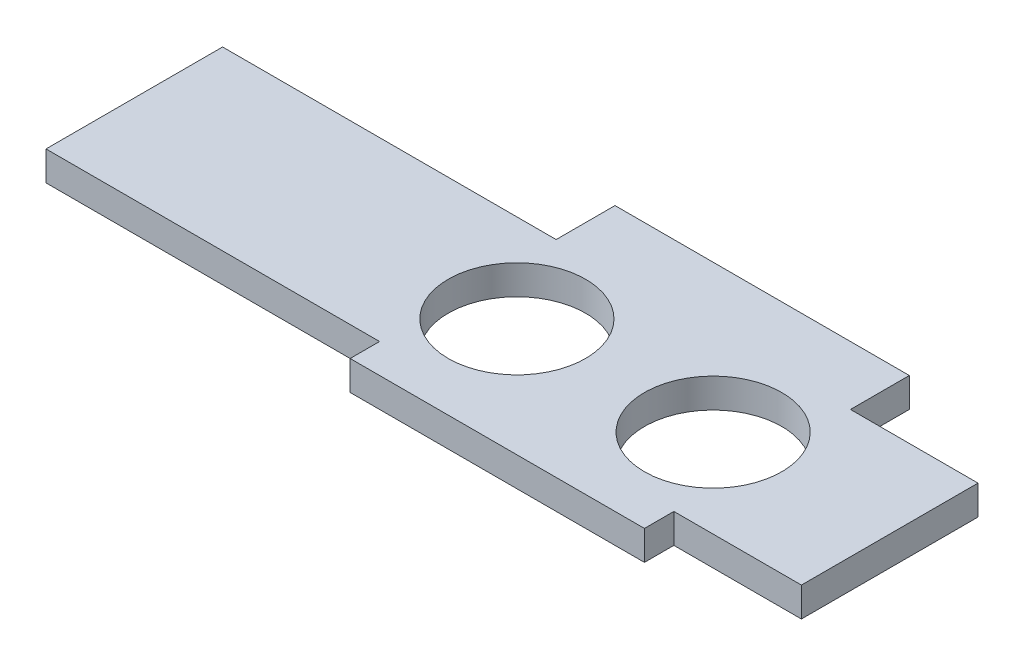
SolidWorks part; units mm, degrees
ref_plane "Front Plane" through (0, 0, 0) normal (0, 0, 1) x (1, 0, 0)
ref_plane "Top Plane" through (0, 0, 0) normal (0, 1, 0) x (1, 0, 0)
ref_plane "Right Plane" through (0, 0, 0) normal (1, 0, 0) x (0, 0, -1)
sketch "Sketch1" plane through (0, 0, 0) normal (0, 1, 0) x (1, 0, 0)
  line L0 (-3, 0) -> (-3, 50000) construction
  line L1 (3, 0) -> (3, 50000) construction
  line L2 (5, 0) -> (5, 50000) construction
  line L3 (-30.5, 9) -> (5.5, 9)
  line L4 (-30.5, 9) -> (-30.5, -9)
  line L5 (-30.5, -9) -> (5.5, -9)
  line L6 (5.5, 9) -> (5.5, -9) construction
  line L7 (-5, 0) -> (-5, 50000) construction
  line L9 (25.5, 9) -> (-10.5, 9)
  line L10 (25.5, 9) -> (25.5, -9)
  line L11 (25.5, -9) -> (-10.5, -9)
  line L12 (-10.5, 9) -> (-10.5, -9) construction
  line L13 (-30.5, 9) -> (25.5, 9)
  line L14 (-30.5, 9) -> (-30.5, -9)
  line L15 (-30.5, -9) -> (25.5, -9)
  line L16 (25.5, 9) -> (25.5, -9)
  circle A0 centre (0, 0) radius 3 construction
  circle A1 centre (-12.5, 0) radius 7
  circle A2 centre (7.5, 0) radius 7
  circle A3 centre (-10, 0) radius 15 construction
  circle A4 centre (10, 0) radius 15 construction
  point P11 (-30.5, 0)
  point P18 (-12.5, 9)
  point P25 (9.3539, 9)
  point P26 (7.5, 9)
  point P28 (25.5, 0)
  dimension "D1" = 6
  dimension "D2" = 36
  dimension "D5" = 14
  dimension "D6" = 14
  dimension "D9" = 2
  dimension "D7" = 2
  dimension "D8" = 7
  dimension "D10" = 12.5
  dimension "D3" = 7
  dimension "D4" = 18
  dimension "D11" = 7.5
  dimension "D12" = 36
extrude "BaseShape" add sketch "Sketch1" along normal blind 3 contours A2 | L14 L13 L16 L15 | A1 region at (7.5, 0, 0)
sketch "Sketch2" plane through (0, 0, 0) normal (0, -1, 0) x (1, 0, 0)
  line L0 (-30.5, -9) -> (25.5, -9) construction
  line L1 (-30.5, -9) -> (-51.5, -9)
  line L2 (-30.5, -9) -> (-30.5, 9)
  line L3 (-30.5, 9) -> (-51.5, 9)
  line L4 (-51.5, -9) -> (-51.5, 9)
  line L5 (-17.5, -9) -> (12.5, -9)
  line L6 (-17.5, -9) -> (-17.5, -15)
  line L7 (-17.5, -15) -> (12.5, -15)
  line L8 (12.5, -9) -> (12.5, -15)
  line L9 (-30.5, -9) -> (-17.5, -9) construction
  line L10 (12.5, -9) -> (25.5, -9) construction
  line L11 (-17.5, 9) -> (-17.5, 12)
  line L12 (-30.5, 9) -> (25.5, 9) construction
  line L13 (-17.5, 12) -> (12.5, 12)
  line L14 (12.5, 12) -> (12.5, 9)
  line L15 (12.5, 9) -> (-17.5, 9)
  dimension "D1" = 21
  dimension "D2" = 6
  dimension "D3" = 30
  dimension "D4" = 3
extrude "FingerJoints" add sketch "Sketch2" against normal up to surface (3 mm away) up to face at (-2.5, 3, 0)
